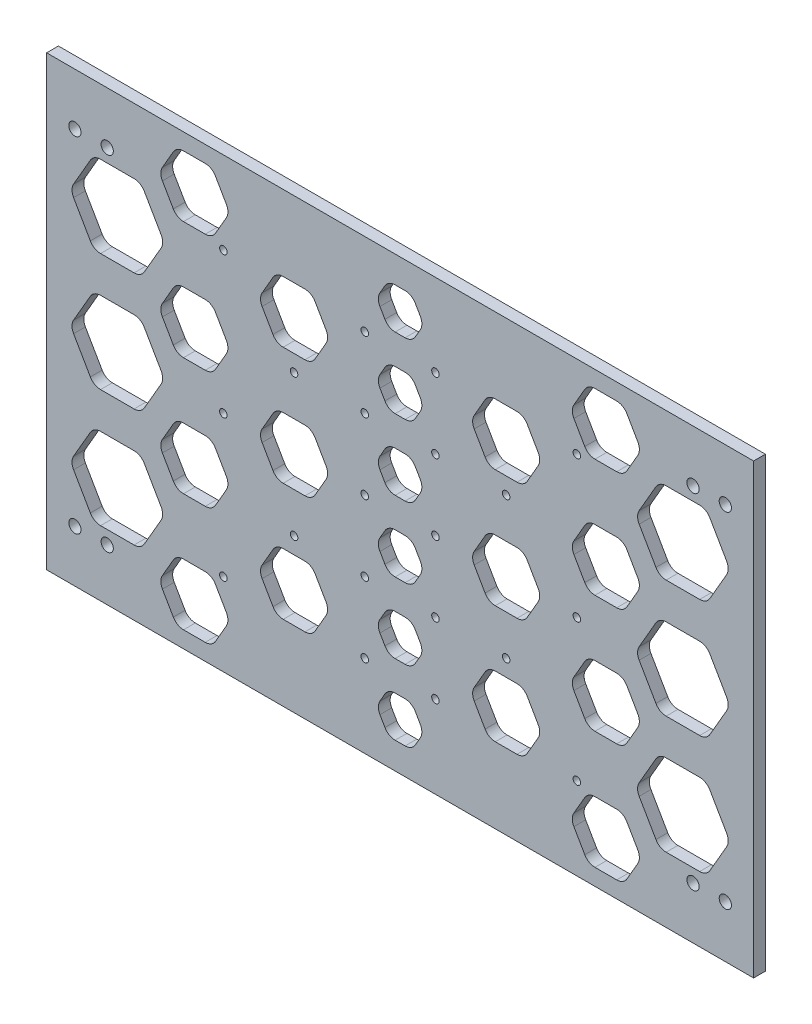
SolidWorks part; units mm, degrees
ref_plane "前视基准面" through (0, 0, 0) normal (0, 0, 1) x (1, 0, 0)
ref_plane "上视基准面" through (0, 0, 0) normal (0, 1, 0) x (1, 0, 0)
ref_plane "右视基准面" through (0, 0, 0) normal (1, 0, 0) x (0, 0, -1)
other "Configuration Table"
sketch "草图1" plane through (0, 0, 0) normal (0, 0, 1) x (1, 0, 0)
  line L0 (0, -95) -> (300, -95) construction
  line L1 (0, 0) -> (300, 0)
  line L2 (0, 0) -> (0, -190)
  line L3 (0, -190) -> (300, -190)
  line L4 (300, 0) -> (300, -190)
  line L5 (50, 0) -> (250, 0)
  line L6 (50, 0) -> (50, -50)
  line L7 (50, -50) -> (250, -50)
  line L8 (250, 0) -> (250, -50)
  line L9 (250, -190) -> (250, -140)
  line L10 (50, -140) -> (250, -140)
  line L11 (50, -190) -> (50, -140)
  dimension "D1" = 300
  dimension "D2" = 190
  dimension "D3" = 50
  dimension "D4" = 50
  dimension "D5" = 50
extrude "凸台-拉伸2" add sketch "草图1" along normal blind 5 contours L2 L0 L4 L1 L8 L7 L6 | L0 L2 L3 L11 L10 L9 L4 region at (150, -59.6622, 0) region at (150, -130.3378, 0)
sketch "草图2" plane through (0, 0, 5) normal (0, 0, 1) x (1, 0, 0)
  line L0 (0, -95) -> (300, -95) construction
  line L1 (150, -50) -> (150, -140) construction
  line L2 (0, -35) -> (5, -35)
  line L3 (0, -35) -> (0, -65)
  line L4 (0, -65) -> (5, -65)
  line L5 (5, -35) -> (5, -65)
  line L6 (0, -155) -> (5, -155)
  line L7 (5, -155) -> (5, -125)
  line L8 (0, -125) -> (5, -125)
  line L9 (300, -155) -> (295, -155)
  line L10 (295, -155) -> (295, -125)
  line L11 (300, -125) -> (295, -125)
  line L12 (0, 0) -> (0, -190)
  line L13 (0, -190) -> (50, -190)
  line L14 (50, -190) -> (50, -140)
  line L15 (50, -140) -> (250, -140)
  line L16 (250, -140) -> (250, -190)
  line L17 (250, -190) -> (300, -190)
  line L18 (300, -190) -> (300, 0)
  line L19 (300, 0) -> (250, 0)
  line L20 (250, 0) -> (250, -50)
  line L21 (250, -50) -> (50, -50)
  line L22 (50, -50) -> (50, 0)
  line L23 (50, 0) -> (0, 0)
  line L24 (0, 0) -> (0, -190)
  line L25 (0, -190) -> (50, -190)
  line L26 (50, -190) -> (50, -140)
  line L27 (50, -140) -> (250, -140)
  line L28 (250, -140) -> (250, -190)
  line L29 (250, -190) -> (300, -190)
  line L30 (300, -190) -> (300, 0)
  line L31 (300, 0) -> (250, 0)
  line L32 (250, 0) -> (250, -50)
  line L33 (250, -50) -> (50, -50)
  line L34 (50, -50) -> (50, 0)
  line L35 (50, 0) -> (0, 0)
  line L36 (300, -65) -> (295, -65)
  line L37 (300, -35) -> (295, -35)
  line L38 (295, -35) -> (295, -65)
  line M22 (0, 0) -> (0, -190)
  line M28 (300, -190) -> (300, 0)
  dimension "D2" = 30
  dimension "D3" = 30
  dimension "D4" = 5
  dimension "D1" = 0
extrude "切除-拉伸1" cut sketch "草图2" against normal blind 10 contours L5 L2 L4 M22 | L8 L6 L7 M22 | L37 L38 L36 L30 | L11 L10 L9 M28 region at (2.5, -50, 5) region at (2.5, -140, 5) region at (297.5, -50, 5) region at (297.5, -140, 5)
sketch "草图3" plane through (0, 0, 5) normal (0, 0, 1) x (1, 0, 0)
  line L0 (150, -50) -> (150, -140) construction
  line L1 (0, -95) -> (300, -95)
  line L28 (0, -65) -> (0, -125)
  line L29 (0, -125) -> (5, -125)
  line L30 (5, -125) -> (5, -155)
  line L31 (5, -155) -> (0, -155)
  line L32 (0, -155) -> (0, -190)
  line L33 (0, -190) -> (50, -190)
  line L34 (50, -190) -> (50, -140)
  line L35 (50, -140) -> (250, -140)
  line L36 (250, -140) -> (250, -190)
  line L37 (250, -190) -> (300, -190)
  line L38 (300, -190) -> (300, -155)
  line L39 (300, -155) -> (295, -155)
  line L40 (295, -155) -> (295, -125)
  line L41 (295, -125) -> (300, -125)
  line L42 (300, -125) -> (300, -65)
  line L43 (300, -65) -> (295, -65)
  line L44 (295, -65) -> (295, -35)
  line L45 (295, -35) -> (300, -35)
  line L46 (300, -35) -> (300, 0)
  line L47 (300, 0) -> (250, 0)
  line L48 (250, 0) -> (250, -50)
  line L49 (250, -50) -> (50, -50)
  line L50 (50, -50) -> (50, 0)
  line L51 (50, 0) -> (0, 0)
  line L52 (0, 0) -> (0, -35)
  line L53 (0, -35) -> (5, -35)
  line L54 (5, -35) -> (5, -65)
  line L55 (5, -65) -> (0, -65)
  line L56 (0, -65) -> (0, -125)
  line L57 (0, -125) -> (5, -125)
  line L58 (5, -125) -> (5, -155)
  line L59 (5, -155) -> (0, -155)
  line L60 (0, -155) -> (0, -190)
  line L61 (0, -190) -> (50, -190)
  line L62 (50, -190) -> (50, -140)
  line L63 (50, -140) -> (250, -140)
  line L64 (250, -140) -> (250, -190)
  line L65 (250, -190) -> (300, -190)
  line L66 (300, -190) -> (300, -155)
  line L67 (300, -155) -> (295, -155)
  line L68 (295, -155) -> (295, -125)
  line L69 (295, -125) -> (300, -125)
  line L70 (300, -125) -> (300, -65)
  line L71 (300, -65) -> (295, -65)
  line L72 (295, -65) -> (295, -35)
  line L73 (295, -35) -> (300, -35)
  line L74 (300, -35) -> (300, 0)
  line L75 (300, 0) -> (250, 0)
  line L76 (250, 0) -> (250, -50)
  line L77 (250, -50) -> (50, -50)
  line L78 (50, -50) -> (50, 0)
  line L79 (50, 0) -> (0, 0)
  line L80 (0, 0) -> (0, -35)
  line L81 (0, -35) -> (5, -35)
  line L82 (5, -35) -> (5, -65)
  line L83 (5, -65) -> (0, -65)
  circle A0 centre (5, -35) radius 1
  circle A1 centre (5, -65) radius 1
  circle A2 centre (5, -125) radius 1
  circle A3 centre (5, -155) radius 1
  circle A4 centre (295, -35) radius 1
  circle A5 centre (295, -65) radius 1
  circle A6 centre (295, -125) radius 1
  circle A7 centre (295, -155) radius 1
  line M31 (5, -125) -> (5, -155)
  line M32 (5, -155) -> (0, -155)
  line M41 (295, -155) -> (295, -125)
  line M42 (295, -125) -> (300, -125)
  line M45 (295, -65) -> (295, -35)
  line M46 (295, -35) -> (300, -35)
  line M55 (5, -35) -> (5, -65)
  line M56 (5, -65) -> (0, -65)
  dimension "D2" = 2
  dimension "D3" = 2
  dimension "D1" = 0
extrude "切除-拉伸2" cut sketch "草图3" against normal blind 10 contours A0 L81 M55 | L81 A0 M55 | A1 M56 M55 | A2 L57 M31 | A3 M31 M32 | A7 L67 M41 | A6 L68 M42 | A4 L72 M46 | A5 L71 M45 region at (5.1415, -65.1415, 5) region at (5.1415, -124.8585, 5) region at (294.8585, -124.8585, 5) region at (294.8585, -65.1415, 5) region at (4.5756, -35.4244, 5) region at (5.1415, -34.8585, 5) region at (5.1415, -155.1415, 5) region at (294.8585, -155.1415, 5) region at (294.8585, -34.8585, 5)
sketch "草图4" plane through (50, 0, 0) normal (1, 0, 0) x (0, 0, -1)
  line L4 (0, -50) -> (0, 0)
  line L5 (0, 0) -> (-5, 0)
  line L6 (-5, 0) -> (-5, -50)
  line L7 (-5, -50) -> (0, -50)
  line L8 (0, -50) -> (0, 0)
  line L9 (0, 0) -> (-5, 0)
  line L10 (-5, 0) -> (-5, -50)
  line L11 (-5, -50) -> (0, -50)
  line L12 (0, -190) -> (0, -140)
  line L13 (0, -140) -> (-5, -140)
  line L14 (-5, -140) -> (-5, -190)
  line L15 (-5, -190) -> (0, -190)
  line L16 (0, -190) -> (0, -140)
  line L17 (0, -140) -> (-5, -140)
  line L18 (-5, -140) -> (-5, -190)
  line L19 (-5, -190) -> (0, -190)
  dimension "D1" = 0
  dimension "D2" = 0
extrude "凸台-拉伸3" add sketch "草图4" along normal up to next
sketch "草图5" plane through (0, 0, 5) normal (0, 0, 1) x (1, 0, 0)
  line L0 (150, 0) -> (150, -190)
  line L1 (32.7, -35) -> (37.7, -35)
  line L2 (32.7, -35) -> (32.7, -65)
  line L3 (32.7, -65) -> (37.7, -65)
  line L4 (37.7, -35) -> (37.7, -65)
  line L5 (0, -95) -> (300, -95)
  line L6 (32.7, -125) -> (37.7, -125)
  line L7 (37.7, -155) -> (37.7, -125)
  line L8 (32.7, -155) -> (37.7, -155)
  line L9 (32.7, -155) -> (32.7, -125)
  line L10 (267.3, -155) -> (267.3, -125)
  line L11 (267.3, -155) -> (262.3, -155)
  line L12 (262.3, -155) -> (262.3, -125)
  line L13 (267.3, -125) -> (262.3, -125)
  line L14 (267.3, -65) -> (262.3, -65)
  line L15 (262.3, -35) -> (262.3, -65)
  line L16 (267.3, -35) -> (262.3, -35)
  line L17 (267.3, -35) -> (267.3, -65)
  line L20 (300, 0) -> (0, 0)
  line L21 (0, 0) -> (0, -35)
  line L22 (0, -35) -> (4, -35)
  line L23 (5, -36) -> (5, -64)
  line L24 (4, -65) -> (0, -65)
  line L25 (0, -65) -> (0, -125)
  line L26 (0, -125) -> (4, -125)
  line L27 (5, -126) -> (5, -154)
  line L28 (4, -155) -> (0, -155)
  line L29 (0, -155) -> (0, -190)
  line L30 (0, -190) -> (300, -190)
  line L31 (300, -190) -> (300, -155)
  line L32 (300, -155) -> (296, -155)
  line L33 (295, -154) -> (295, -126)
  line L34 (296, -125) -> (300, -125)
  line L35 (300, -125) -> (300, -65)
  line L36 (300, -65) -> (296, -65)
  line L37 (295, -64) -> (295, -36)
  line L38 (296, -35) -> (300, -35)
  line L39 (300, -35) -> (300, 0)
  line L40 (300, 0) -> (0, 0)
  line L41 (0, 0) -> (0, -35)
  line L42 (0, -35) -> (4, -35)
  line L43 (5, -36) -> (5, -64)
  line L44 (4, -65) -> (0, -65)
  line L45 (0, -65) -> (0, -125)
  line L46 (0, -125) -> (4, -125)
  line L47 (5, -126) -> (5, -154)
  line L48 (4, -155) -> (0, -155)
  line L49 (0, -155) -> (0, -190)
  line L50 (0, -190) -> (300, -190)
  line L51 (300, -190) -> (300, -155)
  line L52 (300, -155) -> (296, -155)
  line L53 (295, -154) -> (295, -126)
  line L54 (296, -125) -> (300, -125)
  line L55 (300, -125) -> (300, -65)
  line L56 (300, -65) -> (296, -65)
  line L57 (295, -64) -> (295, -36)
  line L58 (296, -35) -> (300, -35)
  line L59 (300, -35) -> (300, 0)
  circle A0 centre (32.7, -35) radius 1
  circle A1 centre (37.7, -35) radius 1
  circle A2 centre (32.7, -65) radius 1
  circle A3 centre (37.7, -65) radius 1
  circle A4 centre (37.7, -125) radius 1
  circle A5 centre (32.7, -125) radius 1
  circle A6 centre (37.7, -155) radius 1
  circle A7 centre (32.7, -155) radius 1
  arc A8 (5, -36) -> (4, -35) centre (5, -35) ccw
  arc A9 (4, -65) -> (5, -64) centre (5, -65) ccw
  arc A10 (5, -126) -> (4, -125) centre (5, -125) ccw
  arc A11 (4, -155) -> (5, -154) centre (5, -155) ccw
  arc A12 (295, -154) -> (296, -155) centre (295, -155) ccw
  arc A13 (296, -125) -> (295, -126) centre (295, -125) ccw
  arc A14 (295, -64) -> (296, -65) centre (295, -65) ccw
  arc A15 (296, -35) -> (295, -36) centre (295, -35) ccw
  arc A16 (5, -36) -> (4, -35) centre (5, -35) ccw
  arc A17 (4, -65) -> (5, -64) centre (5, -65) ccw
  arc A18 (5, -126) -> (4, -125) centre (5, -125) ccw
  arc A19 (4, -155) -> (5, -154) centre (5, -155) ccw
  arc A20 (295, -154) -> (296, -155) centre (295, -155) ccw
  arc A21 (296, -125) -> (295, -126) centre (295, -125) ccw
  arc A22 (295, -64) -> (296, -65) centre (295, -65) ccw
  arc A23 (296, -35) -> (295, -36) centre (295, -35) ccw
  circle A24 centre (262.3, -155) radius 1
  circle A25 centre (267.3, -155) radius 1
  circle A26 centre (262.3, -125) radius 1
  circle A27 centre (267.3, -125) radius 1
  circle A28 centre (262.3, -35) radius 1
  circle A29 centre (267.3, -35) radius 1
  circle A30 centre (267.3, -65) radius 1
  circle A31 centre (262.3, -65) radius 1
  dimension "D4" = 2
  dimension "D5" = 2
  dimension "D6" = 2
  dimension "D7" = 2
  dimension "D2" = 32.7
  dimension "D3" = 5
  dimension "D1" = 0
extrude "切除-拉伸3" cut sketch "草图5" against normal blind 5 contours A3 L4 A1 L1 A0 L2 A2 L3 | L1 A0 L2 | L4 A1 L1 | L1 A1 L4 | L2 A0 L1 | L3 A2 L2 | L2 A2 L3 | L3 A3 L4 | L4 A3 L3 | A7 L8 L9 | A7 L9 L8 | L9 A7 L8 A6 L7 A4 L6 A5 | A6 L8 L7 | A6 L7 L8 | A5 L9 L6 | A5 L6 L9 | A4 L6 L7 | A4 L7 L6 | L15 A31 L14 A30 L17 A29 L16 A28 | A28 L15 L16 | A28 L16 L15 | A29 L17 L16 | A29 L16 L17 | A31 L15 L14 | A31 L14 L15 | A30 L17 L14 | A30 L14 L17 | L13 A26 L12 | L12 A26 L13 | A27 L13 A26 L12 A24 L11 A25 L10 | L13 A27 L10 | L10 A27 L13 | L12 A24 L11 | L11 A24 L12 | L11 A25 L10 | L10 A25 L11 region at (32.5585, -34.8585, 5) region at (33.1244, -35.4244, 5) region at (35.2, -50, 5) region at (37.8415, -34.8585, 5) region at (37.2756, -35.4244, 5) region at (33.1244, -64.5756, 5) region at (32.5585, -65.1415, 5) region at (37.8415, -65.1415, 5) region at (37.2756, -64.5756, 5) region at (32.5585, -124.8585, 5) region at (33.1244, -125.4244, 5) region at (35.2, -140, 5) region at (37.8415, -124.8585, 5) region at (37.2756, -125.4244, 5) region at (33.1244, -154.5756, 5) region at (32.5585, -155.1415, 5) region at (37.8415, -155.1415, 5) region at (37.2756, -154.5756, 5) region at (266.8756, -154.5756, 5) region at (267.4415, -155.1415, 5) region at (264.8, -140, 5) region at (266.8756, -125.4244, 5) region at (267.4415, -124.8585, 5) region at (262.1585, -155.1415, 5) region at (262.7244, -154.5756, 5) region at (262.7244, -125.4244, 5) region at (262.1585, -124.8585, 5) region at (262.1585, -65.1415, 5) region at (264.8, -50, 5) region at (262.7244, -64.5756, 5) region at (266.8756, -64.5756, 5) region at (267.4415, -65.1415, 5) region at (262.1585, -34.8585, 5) region at (262.7244, -35.4244, 5) region at (266.8756, -35.4244, 5) region at (267.4415, -34.8585, 5)
sketch "草图6" plane through (0, 0, 5) normal (0, 0, 1) x (1, 0, 0)
  line L0 (4, -160) -> (127.3647, -160)
  line L1 (32.7, -154) -> (32.7, -126) construction
  line L2 (0, -95) -> (300, -95)
  line L3 (150, 0) -> (150, -190)
  line L20 (300, 0) -> (0, 0)
  line L21 (0, 0) -> (0, -35)
  line L22 (0, -35) -> (4, -35)
  line L23 (5, -36) -> (5, -64)
  line L24 (4, -65) -> (0, -65)
  line L25 (0, -65) -> (0, -125)
  line L26 (0, -125) -> (4, -125)
  line L27 (5, -126) -> (5, -154)
  line L28 (4, -155) -> (0, -155)
  line L29 (0, -155) -> (0, -190)
  line L30 (0, -190) -> (300, -190)
  line L31 (300, -190) -> (300, -155)
  line L32 (300, -155) -> (296, -155)
  line L33 (295, -154) -> (295, -126)
  line L34 (296, -125) -> (300, -125)
  line L35 (300, -125) -> (300, -65)
  line L36 (300, -65) -> (296, -65)
  line L37 (295, -64) -> (295, -36)
  line L38 (296, -35) -> (300, -35)
  line L39 (300, -35) -> (300, 0)
  line L40 (300, 0) -> (0, 0)
  line L41 (0, 0) -> (0, -35)
  line L42 (0, -35) -> (4, -35)
  line L43 (5, -36) -> (5, -64)
  line L44 (4, -65) -> (0, -65)
  line L45 (0, -65) -> (0, -125)
  line L46 (0, -125) -> (4, -125)
  line L47 (5, -126) -> (5, -154)
  line L48 (4, -155) -> (0, -155)
  line L49 (0, -155) -> (0, -190)
  line L50 (0, -190) -> (300, -190)
  line L51 (300, -190) -> (300, -155)
  line L52 (300, -155) -> (296, -155)
  line L53 (295, -154) -> (295, -126)
  line L54 (296, -125) -> (300, -125)
  line L55 (300, -125) -> (300, -65)
  line L56 (300, -65) -> (296, -65)
  line L57 (295, -64) -> (295, -36)
  line L58 (296, -35) -> (300, -35)
  line L59 (300, -35) -> (300, 0)
  circle A0 centre (12, -168) radius 2.6
  circle A1 centre (25.7, -168) radius 2.6
  circle A2 centre (25.7, -22) radius 2.6
  circle A3 centre (12, -22) radius 2.6
  circle A4 centre (274.3, -168) radius 2.6
  circle A5 centre (288, -168) radius 2.6
  circle A6 centre (274.3, -22) radius 2.6
  circle A7 centre (288, -22) radius 2.6
  arc A8 (5, -36) -> (4, -35) centre (5, -35) ccw
  arc A9 (4, -65) -> (5, -64) centre (5, -65) ccw
  arc A10 (5, -126) -> (4, -125) centre (5, -125) ccw
  arc A11 (4, -155) -> (5, -154) centre (5, -155) ccw
  arc A12 (295, -154) -> (296, -155) centre (295, -155) ccw
  arc A13 (296, -125) -> (295, -126) centre (295, -125) ccw
  arc A14 (295, -64) -> (296, -65) centre (295, -65) ccw
  arc A15 (296, -35) -> (295, -36) centre (295, -35) ccw
  arc A16 (5, -36) -> (4, -35) centre (5, -35) ccw
  arc A17 (4, -65) -> (5, -64) centre (5, -65) ccw
  arc A18 (5, -126) -> (4, -125) centre (5, -125) ccw
  arc A19 (4, -155) -> (5, -154) centre (5, -155) ccw
  arc A20 (295, -154) -> (296, -155) centre (295, -155) ccw
  arc A21 (296, -125) -> (295, -126) centre (295, -125) ccw
  arc A22 (295, -64) -> (296, -65) centre (295, -65) ccw
  arc A23 (296, -35) -> (295, -36) centre (295, -35) ccw
  dimension "D3" = 5.2
  dimension "D4" = 5.2
  dimension "D5" = 8
  dimension "D2" = 30
  dimension "D6" = 7
  dimension "D7" = 8
  dimension "D8" = 7
  dimension "D1" = 0
extrude "切除-拉伸4" cut sketch "草图6" against normal through all contours A3 | A2 | A0 | A1 | A4 | A5 | A6 | A7 region at (12, -168, 5) region at (25.7, -168, 5) region at (25.7, -22, 5) region at (12, -22, 5) region at (274.3, -168, 5) region at (288, -168, 5) region at (274.3, -22, 5) region at (288, -22, 5)
sketch "草图7" plane through (0, 0, 5) normal (0, 0, 1) x (1, 0, 0)
  line L1 (0, 0) -> (300, 0) construction
  line L6 (300, 0) -> (300, -35) construction
  circle A0 centre (75, -35) radius 1.6
  circle A1 centre (105, -35) radius 1.6
  circle A2 centre (135, -35) radius 1.6
  circle A3 centre (165, -35) radius 1.6
  circle A4 centre (195, -35) radius 1.6
  circle A5 centre (225, -35) radius 1.6
  circle A6 centre (105, -65) radius 1.6
  circle A7 centre (135, -65) radius 1.6
  circle A8 centre (165, -65) radius 1.6
  circle A9 centre (195, -65) radius 1.6
  circle A10 centre (225, -65) radius 1.6
  circle A11 centre (105, -95) radius 1.6
  circle A12 centre (135, -95) radius 1.6
  circle A13 centre (165, -95) radius 1.6
  circle A14 centre (195, -95) radius 1.6
  circle A15 centre (225, -95) radius 1.6
  circle A16 centre (105, -125) radius 1.6
  circle A17 centre (135, -125) radius 1.6
  circle A18 centre (165, -125) radius 1.6
  circle A19 centre (195, -125) radius 1.6
  circle A20 centre (225, -125) radius 1.6
  circle A21 centre (105, -155) radius 1.6
  circle A22 centre (135, -155) radius 1.6
  circle A23 centre (165, -155) radius 1.6
  circle A24 centre (195, -155) radius 1.6
  circle A25 centre (225, -155) radius 1.6
  circle A26 centre (75, -65) radius 1.6
  circle A27 centre (75, -95) radius 1.6
  circle A28 centre (75, -125) radius 1.6
  circle A29 centre (75, -155) radius 1.6
  dimension "D1" = 3.2
  dimension "D2" = 35
  dimension "D5" = 75
  dimension "D6" = 30
  dimension "D7" = 30
  dimension "D3" = 6
  dimension "D4" = 5
extrude "切除-拉伸5" cut sketch "草图7" against normal through all
sketch "草图8" plane through (0, 0, 5) normal (0, 0, 1) x (1, 0, 0)
  line L4 (267.3, -154) -> (267.3, -126)
  line L5 (263.3, -155) -> (266.3, -155)
  line L6 (262.3, -126) -> (262.3, -154)
  line L7 (266.3, -125) -> (263.3, -125)
  line L8 (267.3, -154) -> (267.3, -126)
  line L9 (263.3, -155) -> (266.3, -155)
  line L10 (262.3, -126) -> (262.3, -154)
  line L11 (266.3, -125) -> (263.3, -125)
  line L12 (32.7, -36) -> (32.7, -64)
  line L13 (36.7, -35) -> (33.7, -35)
  line L14 (37.7, -64) -> (37.7, -36)
  line L15 (33.7, -65) -> (36.7, -65)
  line L16 (32.7, -36) -> (32.7, -64)
  line L17 (36.7, -35) -> (33.7, -35)
  line L18 (37.7, -64) -> (37.7, -36)
  line L19 (33.7, -65) -> (36.7, -65)
  line L20 (263.3, -65) -> (266.3, -65)
  line L21 (262.3, -36) -> (262.3, -64)
  line L22 (266.3, -35) -> (263.3, -35)
  line L23 (267.3, -64) -> (267.3, -36)
  line L24 (263.3, -65) -> (266.3, -65)
  line L25 (262.3, -36) -> (262.3, -64)
  line L26 (266.3, -35) -> (263.3, -35)
  line L27 (267.3, -64) -> (267.3, -36)
  line L28 (36.7, -125) -> (33.7, -125)
  line L29 (37.7, -154) -> (37.7, -126)
  line L30 (33.7, -155) -> (36.7, -155)
  line L31 (32.7, -126) -> (32.7, -154)
  line L32 (36.7, -125) -> (33.7, -125)
  line L33 (37.7, -154) -> (37.7, -126)
  line L34 (33.7, -155) -> (36.7, -155)
  line L35 (32.7, -126) -> (32.7, -154)
  line L52 (300, 0) -> (0, 0)
  line L53 (0, 0) -> (0, -35)
  line L54 (0, -35) -> (4, -35)
  line L55 (5, -36) -> (5, -64)
  line L56 (4, -65) -> (0, -65)
  line L57 (0, -65) -> (0, -125)
  line L58 (0, -125) -> (4, -125)
  line L59 (5, -126) -> (5, -154)
  line L60 (4, -155) -> (0, -155)
  line L61 (0, -155) -> (0, -190)
  line L62 (0, -190) -> (300, -190)
  line L63 (300, -190) -> (300, -155)
  line L64 (300, -155) -> (296, -155)
  line L65 (295, -154) -> (295, -126)
  line L66 (296, -125) -> (300, -125)
  line L67 (300, -125) -> (300, -65)
  line L68 (300, -65) -> (296, -65)
  line L69 (295, -64) -> (295, -36)
  line L70 (296, -35) -> (300, -35)
  line L71 (300, -35) -> (300, 0)
  line L72 (300, 0) -> (0, 0)
  line L73 (0, 0) -> (0, -35)
  line L74 (0, -35) -> (4, -35)
  line L75 (5, -36) -> (5, -64)
  line L76 (4, -65) -> (0, -65)
  line L77 (0, -65) -> (0, -125)
  line L78 (0, -125) -> (4, -125)
  line L79 (5, -126) -> (5, -154)
  line L80 (4, -155) -> (0, -155)
  line L81 (0, -155) -> (0, -190)
  line L82 (0, -190) -> (300, -190)
  line L83 (300, -190) -> (300, -155)
  line L84 (300, -155) -> (296, -155)
  line L85 (295, -154) -> (295, -126)
  line L86 (296, -125) -> (300, -125)
  line L87 (300, -125) -> (300, -65)
  line L88 (300, -65) -> (296, -65)
  line L89 (295, -64) -> (295, -36)
  line L90 (296, -35) -> (300, -35)
  line L91 (300, -35) -> (300, 0)
  circle A1 centre (195, -65) radius 1.6
  circle A2 centre (195, -65) radius 1.6
  circle A3 centre (12, -22) radius 2.6
  circle A4 centre (12, -22) radius 2.6
  circle A5 centre (274.3, -22) radius 2.6
  circle A6 centre (274.3, -22) radius 2.6
  circle A7 centre (288, -22) radius 2.6
  arc A8 (267.3, -126) -> (266.3, -125) centre (267.3, -125) ccw
  arc A9 (266.3, -155) -> (267.3, -154) centre (267.3, -155) ccw
  arc A10 (262.3, -154) -> (263.3, -155) centre (262.3, -155) ccw
  arc A11 (263.3, -125) -> (262.3, -126) centre (262.3, -125) ccw
  arc A12 (267.3, -126) -> (266.3, -125) centre (267.3, -125) ccw
  arc A13 (266.3, -155) -> (267.3, -154) centre (267.3, -155) ccw
  arc A14 (262.3, -154) -> (263.3, -155) centre (262.3, -155) ccw
  arc A15 (263.3, -125) -> (262.3, -126) centre (262.3, -125) ccw
  arc A16 (32.7, -64) -> (33.7, -65) centre (32.7, -65) ccw
  arc A17 (33.7, -35) -> (32.7, -36) centre (32.7, -35) ccw
  arc A18 (37.7, -36) -> (36.7, -35) centre (37.7, -35) ccw
  arc A19 (36.7, -65) -> (37.7, -64) centre (37.7, -65) ccw
  arc A20 (32.7, -64) -> (33.7, -65) centre (32.7, -65) ccw
  arc A21 (33.7, -35) -> (32.7, -36) centre (32.7, -35) ccw
  arc A22 (37.7, -36) -> (36.7, -35) centre (37.7, -35) ccw
  arc A23 (36.7, -65) -> (37.7, -64) centre (37.7, -65) ccw
  arc A24 (266.3, -65) -> (267.3, -64) centre (267.3, -65) ccw
  arc A25 (262.3, -64) -> (263.3, -65) centre (262.3, -65) ccw
  arc A26 (263.3, -35) -> (262.3, -36) centre (262.3, -35) ccw
  arc A27 (267.3, -36) -> (266.3, -35) centre (267.3, -35) ccw
  arc A28 (266.3, -65) -> (267.3, -64) centre (267.3, -65) ccw
  arc A29 (262.3, -64) -> (263.3, -65) centre (262.3, -65) ccw
  arc A30 (263.3, -35) -> (262.3, -36) centre (262.3, -35) ccw
  arc A31 (267.3, -36) -> (266.3, -35) centre (267.3, -35) ccw
  arc A32 (33.7, -125) -> (32.7, -126) centre (32.7, -125) ccw
  arc A33 (37.7, -126) -> (36.7, -125) centre (37.7, -125) ccw
  arc A34 (36.7, -155) -> (37.7, -154) centre (37.7, -155) ccw
  arc A35 (32.7, -154) -> (33.7, -155) centre (32.7, -155) ccw
  arc A36 (33.7, -125) -> (32.7, -126) centre (32.7, -125) ccw
  arc A37 (37.7, -126) -> (36.7, -125) centre (37.7, -125) ccw
  arc A38 (36.7, -155) -> (37.7, -154) centre (37.7, -155) ccw
  arc A39 (32.7, -154) -> (33.7, -155) centre (32.7, -155) ccw
  circle A40 centre (288, -22) radius 2.6
  circle A41 centre (12, -168) radius 2.6
  circle A42 centre (12, -168) radius 2.6
  circle A43 centre (25.7, -168) radius 2.6
  circle A44 centre (25.7, -168) radius 2.6
  circle A45 centre (288, -168) radius 2.6
  circle A46 centre (288, -168) radius 2.6
  circle A47 centre (25.7, -22) radius 2.6
  circle A48 centre (25.7, -22) radius 2.6
  circle A49 centre (274.3, -168) radius 2.6
  circle A50 centre (274.3, -168) radius 2.6
  circle A51 centre (75, -35) radius 1.6
  circle A52 centre (75, -35) radius 1.6
  circle A53 centre (195, -35) radius 1.6
  circle A54 centre (195, -35) radius 1.6
  circle A55 centre (165, -65) radius 1.6
  circle A56 centre (165, -65) radius 1.6
  circle A57 centre (135, -65) radius 1.6
  circle A58 centre (135, -65) radius 1.6
  circle A59 centre (105, -65) radius 1.6
  circle A60 centre (105, -65) radius 1.6
  circle A61 centre (225, -35) radius 1.6
  circle A62 centre (225, -35) radius 1.6
  circle A63 centre (75, -125) radius 1.6
  circle A64 centre (75, -125) radius 1.6
  circle A65 centre (75, -95) radius 1.6
  circle A66 centre (75, -95) radius 1.6
  circle A67 centre (75, -65) radius 1.6
  circle A68 centre (75, -65) radius 1.6
  circle A69 centre (225, -155) radius 1.6
  circle A70 centre (225, -155) radius 1.6
  circle A71 centre (75, -155) radius 1.6
  circle A72 centre (75, -155) radius 1.6
  circle A73 centre (195, -155) radius 1.6
  circle A74 centre (195, -155) radius 1.6
  circle A75 centre (165, -155) radius 1.6
  circle A76 centre (165, -155) radius 1.6
  circle A77 centre (135, -155) radius 1.6
  circle A78 centre (135, -155) radius 1.6
  circle A79 centre (105, -155) radius 1.6
  circle A80 centre (105, -155) radius 1.6
  circle A81 centre (225, -125) radius 1.6
  circle A82 centre (225, -125) radius 1.6
  circle A83 centre (195, -125) radius 1.6
  circle A84 centre (195, -125) radius 1.6
  circle A85 centre (165, -125) radius 1.6
  circle A86 centre (165, -125) radius 1.6
  circle A87 centre (135, -125) radius 1.6
  circle A88 centre (135, -125) radius 1.6
  circle A89 centre (165, -35) radius 1.6
  circle A90 centre (165, -35) radius 1.6
  circle A91 centre (135, -35) radius 1.6
  circle A92 centre (135, -35) radius 1.6
  circle A93 centre (105, -35) radius 1.6
  circle A94 centre (105, -35) radius 1.6
  circle A95 centre (165, -95) radius 1.6
  circle A96 centre (165, -95) radius 1.6
  circle A97 centre (195, -95) radius 1.6
  circle A98 centre (195, -95) radius 1.6
  circle A99 centre (105, -125) radius 1.6
  circle A100 centre (105, -125) radius 1.6
  circle A101 centre (225, -95) radius 1.6
  circle A102 centre (225, -95) radius 1.6
  circle A103 centre (135, -95) radius 1.6
  circle A104 centre (135, -95) radius 1.6
  circle A105 centre (105, -95) radius 1.6
  circle A106 centre (105, -95) radius 1.6
  circle A107 centre (225, -65) radius 1.6
  circle A108 centre (225, -65) radius 1.6
  arc A116 (5, -36) -> (4, -35) centre (5, -35) ccw
  arc A117 (4, -65) -> (5, -64) centre (5, -65) ccw
  arc A118 (5, -126) -> (4, -125) centre (5, -125) ccw
  arc A119 (4, -155) -> (5, -154) centre (5, -155) ccw
  arc A120 (295, -154) -> (296, -155) centre (295, -155) ccw
  arc A121 (296, -125) -> (295, -126) centre (295, -125) ccw
  arc A122 (295, -64) -> (296, -65) centre (295, -65) ccw
  arc A123 (296, -35) -> (295, -36) centre (295, -35) ccw
  arc A124 (5, -36) -> (4, -35) centre (5, -35) ccw
  arc A125 (4, -65) -> (5, -64) centre (5, -65) ccw
  arc A126 (5, -126) -> (4, -125) centre (5, -125) ccw
  arc A127 (4, -155) -> (5, -154) centre (5, -155) ccw
  arc A128 (295, -154) -> (296, -155) centre (295, -155) ccw
  arc A129 (296, -125) -> (295, -126) centre (295, -125) ccw
  arc A130 (295, -64) -> (296, -65) centre (295, -65) ccw
  arc A131 (296, -35) -> (295, -36) centre (295, -35) ccw
  dimension "D1" = 0
  dimension "D2" = 0
  dimension "D3" = 0
  dimension "D4" = 0
  dimension "D5" = 0
  dimension "D6" = 0
  dimension "D7" = 0
  dimension "D8" = 0
  dimension "D9" = 0
  dimension "D10" = 0
  dimension "D11" = 0
  dimension "D12" = 0
  dimension "D13" = 0
  dimension "D14" = 0
  dimension "D15" = 0
  dimension "D16" = 0
  dimension "D17" = 0
  dimension "D18" = 0
  dimension "D19" = 0
  dimension "D20" = 0
  dimension "D21" = 0
  dimension "D22" = 0
  dimension "D23" = 0
  dimension "D24" = 0
  dimension "D25" = 0
  dimension "D26" = 0
  dimension "D27" = 0
  dimension "D28" = 0
  dimension "D29" = 0
  dimension "D30" = 0
  dimension "D31" = 0
  dimension "D32" = 0
  dimension "D33" = 0
  dimension "D34" = 0
  dimension "D35" = 0
  dimension "D36" = 0
  dimension "D37" = 0
  dimension "D38" = 0
  dimension "D39" = 0
  dimension "D40" = 0
  dimension "D41" = 0
  dimension "D42" = 0
  dimension "D43" = 0
sketch "草图9" plane through (0, 0, 5) normal (0, 0, 1) x (1, 0, 0)
  line L0 (300, 0) -> (0, 0) construction
  line L1 (77.7, -20.0004) -> (70.2, -7.01)
  line L2 (70.2, -7.01) -> (55.2, -7.01)
  line L3 (55.2, -7.01) -> (47.7, -20.0004)
  line L4 (47.7, -20.0004) -> (55.2, -32.9908)
  line L5 (55.2, -32.9908) -> (70.2, -32.9908)
  line L6 (70.2, -32.9908) -> (77.7, -20.0004)
  line L7 (37.7, -64) -> (37.7, -36) construction
  line L8 (77.7, -70.0004) -> (70.2, -57.01)
  line L9 (70.2, -57.01) -> (55.2, -57.01)
  line L10 (55.2, -57.01) -> (47.7, -70.0004)
  line L11 (47.7, -70.0004) -> (55.2, -82.9908)
  line L12 (55.2, -82.9908) -> (70.2, -82.9908)
  line L13 (70.2, -82.9908) -> (77.7, -70.0004)
  line L14 (77.7, -120.0004) -> (70.2, -107.01)
  line L15 (70.2, -107.01) -> (55.2, -107.01)
  line L16 (55.2, -107.01) -> (47.7, -120.0004)
  line L17 (47.7, -120.0004) -> (55.2, -132.9908)
  line L18 (55.2, -132.9908) -> (70.2, -132.9908)
  line L19 (70.2, -132.9908) -> (77.7, -120.0004)
  line L20 (77.7, -170.0004) -> (70.2, -157.01)
  line L21 (70.2, -157.01) -> (55.2, -157.01)
  line L22 (55.2, -157.01) -> (47.7, -170.0004)
  line L23 (47.7, -170.0004) -> (55.2, -182.9908)
  line L24 (55.2, -182.9908) -> (70.2, -182.9908)
  line L25 (70.2, -182.9908) -> (77.7, -170.0004)
  line L26 (150, 0) -> (150, -190)
  line L27 (0, -95) -> (300, -95)
  line L28 (120, -45) -> (112.5, -32.0096)
  line L29 (112.5, -32.0096) -> (97.5, -32.0096)
  line L30 (97.5, -32.0096) -> (90, -45)
  line L31 (90, -45) -> (97.5, -57.9904)
  line L32 (97.5, -57.9904) -> (112.5, -57.9904)
  line L33 (112.5, -57.9904) -> (120, -45)
  line L34 (112.5, -82.0096) -> (97.5, -82.0096)
  line L35 (97.5, -82.0096) -> (90, -95)
  line L36 (90, -95) -> (97.5, -107.9904)
  line L37 (97.5, -107.9904) -> (112.5, -107.9904)
  line L38 (112.5, -107.9904) -> (120, -95)
  line L39 (120, -95) -> (112.5, -82.0096)
  line L46 (300, 0) -> (0, 0)
  line L47 (0, 0) -> (0, -35)
  line L48 (0, -35) -> (4, -35)
  line L49 (5, -36) -> (5, -64)
  line L50 (4, -65) -> (0, -65)
  line L51 (0, -65) -> (0, -125)
  line L52 (0, -125) -> (4, -125)
  line L53 (5, -126) -> (5, -154)
  line L54 (4, -155) -> (0, -155)
  line L55 (0, -155) -> (0, -190)
  line L56 (0, -190) -> (300, -190)
  line L57 (300, -190) -> (300, -155)
  line L58 (300, -155) -> (296, -155)
  line L59 (295, -154) -> (295, -126)
  line L60 (296, -125) -> (300, -125)
  line L61 (300, -125) -> (300, -65)
  line L62 (300, -65) -> (296, -65)
  line L63 (295, -64) -> (295, -36)
  line L64 (296, -35) -> (300, -35)
  line L65 (300, -35) -> (300, 0)
  line L66 (300, 0) -> (0, 0)
  line L67 (0, 0) -> (0, -35)
  line L68 (0, -35) -> (4, -35)
  line L69 (5, -36) -> (5, -64)
  line L70 (4, -65) -> (0, -65)
  line L71 (0, -65) -> (0, -125)
  line L72 (0, -125) -> (4, -125)
  line L73 (5, -126) -> (5, -154)
  line L74 (4, -155) -> (0, -155)
  line L75 (0, -155) -> (0, -190)
  line L76 (0, -190) -> (300, -190)
  line L77 (300, -190) -> (300, -155)
  line L78 (300, -155) -> (296, -155)
  line L79 (295, -154) -> (295, -126)
  line L80 (296, -125) -> (300, -125)
  line L81 (300, -125) -> (300, -65)
  line L82 (300, -65) -> (296, -65)
  line L83 (295, -64) -> (295, -36)
  line L84 (296, -35) -> (300, -35)
  line L85 (300, -35) -> (300, 0)
  line L86 (112.5, -157.9904) -> (97.5, -157.9904)
  line L87 (97.5, -157.9904) -> (90, -145)
  line L88 (90, -145) -> (97.5, -132.0096)
  line L89 (97.5, -132.0096) -> (112.5, -132.0096)
  line L90 (112.5, -132.0096) -> (120, -145)
  line L91 (120, -145) -> (112.5, -157.9904)
  line L92 (229.8, -182.9908) -> (222.3, -170.0004)
  line L93 (244.8, -182.9908) -> (229.8, -182.9908)
  line L94 (252.3, -170.0004) -> (244.8, -182.9908)
  line L95 (244.8, -157.01) -> (252.3, -170.0004)
  line L96 (229.8, -157.01) -> (244.8, -157.01)
  line L97 (222.3, -170.0004) -> (229.8, -157.01)
  line L98 (180, -145) -> (187.5, -157.9904)
  line L99 (187.5, -132.0096) -> (180, -145)
  line L100 (202.5, -132.0096) -> (187.5, -132.0096)
  line L101 (210, -145) -> (202.5, -132.0096)
  line L102 (202.5, -157.9904) -> (210, -145)
  line L103 (187.5, -157.9904) -> (202.5, -157.9904)
  line L104 (229.8, -132.9908) -> (222.3, -120.0004)
  line L105 (244.8, -132.9908) -> (229.8, -132.9908)
  line L106 (252.3, -120.0004) -> (244.8, -132.9908)
  line L107 (244.8, -107.01) -> (252.3, -120.0004)
  line L108 (229.8, -107.01) -> (244.8, -107.01)
  line L109 (222.3, -120.0004) -> (229.8, -107.01)
  line L110 (180, -95) -> (187.5, -82.0096)
  line L111 (187.5, -107.9904) -> (180, -95)
  line L112 (202.5, -107.9904) -> (187.5, -107.9904)
  line L113 (210, -95) -> (202.5, -107.9904)
  line L114 (202.5, -82.0096) -> (210, -95)
  line L115 (187.5, -82.0096) -> (202.5, -82.0096)
  line L116 (229.8, -82.9908) -> (222.3, -70.0004)
  line L117 (244.8, -82.9908) -> (229.8, -82.9908)
  line L118 (252.3, -70.0004) -> (244.8, -82.9908)
  line L119 (244.8, -57.01) -> (252.3, -70.0004)
  line L120 (229.8, -57.01) -> (244.8, -57.01)
  line L121 (222.3, -70.0004) -> (229.8, -57.01)
  line L122 (187.5, -57.9904) -> (180, -45)
  line L123 (202.5, -57.9904) -> (187.5, -57.9904)
  line L124 (210, -45) -> (202.5, -57.9904)
  line L125 (202.5, -32.0096) -> (210, -45)
  line L126 (187.5, -32.0096) -> (202.5, -32.0096)
  line L127 (180, -45) -> (187.5, -32.0096)
  line L128 (229.8, -32.9908) -> (222.3, -20.0004)
  line L129 (244.8, -32.9908) -> (229.8, -32.9908)
  line L130 (252.3, -20.0004) -> (244.8, -32.9908)
  line L131 (244.8, -7.01) -> (252.3, -20.0004)
  line L132 (229.8, -7.01) -> (244.8, -7.01)
  line L133 (222.3, -20.0004) -> (229.8, -7.01)
  circle A0 centre (62.7, -20.0004) radius 12.9904 construction
  circle A1 centre (105, -45) radius 12.9904 construction
  circle A2 centre (105, -95) radius 12.9904 construction
  circle A3 centre (105, -145) radius 12.9904 construction
  arc A9 (5, -36) -> (4, -35) centre (5, -35) ccw
  arc A10 (4, -65) -> (5, -64) centre (5, -65) ccw
  arc A11 (5, -126) -> (4, -125) centre (5, -125) ccw
  arc A12 (4, -155) -> (5, -154) centre (5, -155) ccw
  arc A13 (295, -154) -> (296, -155) centre (295, -155) ccw
  arc A14 (296, -125) -> (295, -126) centre (295, -125) ccw
  arc A15 (295, -64) -> (296, -65) centre (295, -65) ccw
  arc A16 (296, -35) -> (295, -36) centre (295, -35) ccw
  arc A17 (5, -36) -> (4, -35) centre (5, -35) ccw
  arc A18 (4, -65) -> (5, -64) centre (5, -65) ccw
  arc A19 (5, -126) -> (4, -125) centre (5, -125) ccw
  arc A20 (4, -155) -> (5, -154) centre (5, -155) ccw
  arc A21 (295, -154) -> (296, -155) centre (295, -155) ccw
  arc A22 (296, -125) -> (295, -126) centre (295, -125) ccw
  arc A23 (295, -64) -> (296, -65) centre (295, -65) ccw
  arc A24 (296, -35) -> (295, -36) centre (295, -35) ccw
  point P12 (37.7, -50)
  dimension "D1" = 15
  dimension "D2" = 7.01
  dimension "D3" = 10
  dimension "D5" = 50
  dimension "D6" = 0
  dimension "D7" = 15
  dimension "D8" = 50
  dimension "D9" = 15
  dimension "D4" = 4
extrude "切除-拉伸6" cut sketch "草图9" against normal blind 10 contours L5 L6 L1 L2 L3 L4 | L32 L33 L28 L29 L30 L31 | L12 L13 L8 L9 L10 L11 | L27 L39 L34 L35 | L18 L19 L14 L15 L16 L17 | L37 L38 L27 L36 | L91 L90 L89 L88 L87 L86 | L24 L25 L20 L21 L22 L23 | L98 L103 L102 L101 L100 L99 | L97 L92 L93 L94 L95 L96 | L109 L104 L105 L106 L107 L108 | L115 L110 L27 L114 | L121 L116 L117 L118 L119 L120 | L113 L27 L111 L112 | L127 L122 L123 L124 L125 L126 | L133 L128 L129 L130 L131 L132 region at (62.7, -20.0004, 5) region at (62.7, -70.0004, 5) region at (62.7, -120.0004, 5) region at (62.7, -170.0004, 5) region at (105, -100.7735, 5) region at (105, -89.2265, 5) region at (195, -89.2265, 5) region at (195, -100.7735, 5) region at (105, -45, 5) region at (105, -145, 5) region at (237.3, -170.0004, 5) region at (195, -145, 5) region at (237.3, -120.0004, 5) region at (237.3, -70.0004, 5) region at (195, -45, 5) region at (237.3, -20.0004, 5)
sketch "草图10" plane through (0, 0, 0) normal (0, 0, -1) x (-1, 0, 0)
  line L0 (-150, 0) -> (-150, -190)
  line L1 (0, 0) -> (-300, 0) construction
  line L2 (0, -190) -> (-300, -190) construction
  line L3 (-160, -50) -> (-155, -58.6603)
  line L4 (-160, -20) -> (-155, -28.6603)
  line L5 (-155, -28.6603) -> (-145, -28.6603)
  line L6 (-145, -28.6603) -> (-140, -20)
  line L7 (-140, -20) -> (-145, -11.3397)
  line L8 (-145, -11.3397) -> (-155, -11.3397)
  line L9 (-155, -11.3397) -> (-160, -20)
  line L10 (-165, -35) -> (-135, -65)
  line L11 (-155, -58.6603) -> (-145, -58.6603)
  line L12 (-145, -58.6603) -> (-140, -50)
  line L13 (-140, -50) -> (-145, -41.3397)
  line L14 (-145, -41.3397) -> (-155, -41.3397)
  line L15 (-155, -41.3397) -> (-160, -50)
  line L16 (-160, -80) -> (-155, -88.6603)
  line L17 (-155, -88.6603) -> (-145, -88.6603)
  line L18 (-145, -88.6603) -> (-140, -80)
  line L19 (-140, -80) -> (-145, -71.3397)
  line L20 (-145, -71.3397) -> (-155, -71.3397)
  line L21 (-155, -71.3397) -> (-160, -80)
  line L22 (-160, -110) -> (-155, -118.6603)
  line L23 (-155, -118.6603) -> (-145, -118.6603)
  line L24 (-145, -118.6603) -> (-140, -110)
  line L25 (-140, -110) -> (-145, -101.3397)
  line L26 (-145, -101.3397) -> (-155, -101.3397)
  line L27 (-155, -101.3397) -> (-160, -110)
  line L28 (-160, -140) -> (-155, -148.6603)
  line L29 (-155, -148.6603) -> (-145, -148.6603)
  line L30 (-145, -148.6603) -> (-140, -140)
  line L31 (-140, -140) -> (-145, -131.3397)
  line L32 (-145, -131.3397) -> (-155, -131.3397)
  line L33 (-155, -131.3397) -> (-160, -140)
  line L34 (-160, -170) -> (-155, -178.6603)
  line L35 (-155, -178.6603) -> (-145, -178.6603)
  line L36 (-145, -178.6603) -> (-140, -170)
  line L37 (-140, -170) -> (-145, -161.3397)
  line L38 (-145, -161.3397) -> (-155, -161.3397)
  line L39 (-155, -161.3397) -> (-160, -170)
  line L40 (-300, -95) -> (0, -95)
  line L41 (-300, -65) -> (-300, -125) construction
  line L42 (0, -65) -> (0, -125) construction
  line L44 (-145, -41.3397) -> (-155, -58.6603)
  circle A0 centre (-150, -20) radius 8.6603 construction
  point P20 (-150, -50)
  dimension "D1" = 10
  dimension "D3" = 30
  dimension "D2" = 6
extrude "切除-拉伸7" cut sketch "草图10" against normal blind 10 contours L25 L26 L0 L23 L24 | L26 L27 L22 L23 L0 | L7 L8 L0 L5 L6 | L8 L9 L4 L5 L0 | L44 L10 L15 L3 | L13 L44 L10 L12 | L44 L14 L0 | L14 L15 L10 L0 | L0 L44 L11 | L11 L12 L10 L0 | L20 L21 L16 L17 L0 | L19 L20 L0 L17 L18 | L31 L32 L0 L29 L30 | L32 L33 L28 L29 L0 | L37 L38 L0 L35 L36 | L38 L39 L34 L35 L0 region at (146.1111, -20, 0) region at (146.1111, -170, 0) region at (153.8889, -170, 0) region at (146.1111, -140, 0) region at (153.8889, -140, 0) region at (146.1111, -110, 0) region at (153.8889, -110, 0) region at (146.1111, -80, 0) region at (153.8889, -80, 0) region at (148.3333, -44.2265, 0) region at (152.404, -44.4964, 0) region at (153.8889, -20, 0) region at (147.596, -55.5036, 0) region at (155.1887, -50.7735, 0) region at (144.8113, -49.2265, 0) region at (151.6667, -55.7735, 0)
sketch "草图11" plane through (0, 0, 0) normal (0, 0, -1) x (-1, 0, 0)
  line L0 (-300, -95) -> (0, -95)
  line L1 (-260, -77.6795) -> (-280, -77.6795)
  line L2 (-280, -77.6795) -> (-290, -95)
  line L3 (-290, -95) -> (-280, -112.3205)
  line L4 (-280, -112.3205) -> (-260, -112.3205)
  line L5 (-260, -112.3205) -> (-250, -95)
  line L6 (-250, -95) -> (-260, -77.6795)
  line L7 (-300, -65) -> (-300, -125) construction
  line L8 (0, -65) -> (0, -125) construction
  line L9 (-150, 0) -> (-150, -190)
  line L10 (0, 0) -> (-300, 0) construction
  line L11 (0, -190) -> (-300, -190) construction
  line L12 (-50, -95) -> (-40, -77.6795)
  line L13 (-40, -112.3205) -> (-50, -95)
  line L14 (-20, -112.3205) -> (-40, -112.3205)
  line L15 (-10, -95) -> (-20, -112.3205)
  line L16 (-20, -77.6795) -> (-10, -95)
  line L17 (-40, -77.6795) -> (-20, -77.6795)
  circle A0 centre (-270, -95) radius 17.3205 construction
  dimension "D1" = 20
  dimension "D2" = 30
extrude "切除-拉伸8" cut sketch "草图11" against normal blind 10 contours L17 L12 L0 L16 | L15 L0 L13 L14 | L0 L6 L1 L2 | L4 L5 L0 L3 region at (270, -87.302, 0) region at (30, -87.302, 0) region at (30, -102.698, 0) region at (270, -102.698, 0)
sketch "草图12" plane through (0, 0, 5) normal (0, 0, 1) x (1, 0, 0)
  line L0 (74.0639, -63.7024) -> (75.6557, -66.4595)
  line L1 (75.656, -123.5407) -> (74.0642, -126.2978)
  line L2 (225.9361, -63.7024) -> (224.3443, -66.4595)
  line L3 (224.344, -123.5407) -> (225.9358, -126.2978)
  line L4 (36.7, -125) -> (33.7, -125)
  line L5 (37.7, -154) -> (37.7, -126)
  line L6 (33.7, -155) -> (36.7, -155)
  line L7 (32.7, -126) -> (32.7, -154)
  line L8 (36.7, -125) -> (33.7, -125)
  line L9 (37.7, -154) -> (37.7, -126)
  line L10 (33.7, -155) -> (36.7, -155)
  line L11 (32.7, -126) -> (32.7, -154)
  line L12 (263.3, -65) -> (266.3, -65)
  line L13 (262.3, -36) -> (262.3, -64)
  line L14 (266.3, -35) -> (263.3, -35)
  line L15 (267.3, -64) -> (267.3, -36)
  line L16 (263.3, -65) -> (266.3, -65)
  line L17 (262.3, -36) -> (262.3, -64)
  line L18 (266.3, -35) -> (263.3, -35)
  line L19 (267.3, -64) -> (267.3, -36)
  line L20 (32.7, -36) -> (32.7, -64)
  line L21 (36.7, -35) -> (33.7, -35)
  line L22 (37.7, -64) -> (37.7, -36)
  line L23 (33.7, -65) -> (36.7, -65)
  line L24 (32.7, -36) -> (32.7, -64)
  line L25 (36.7, -35) -> (33.7, -35)
  line L26 (37.7, -64) -> (37.7, -36)
  line L27 (33.7, -65) -> (36.7, -65)
  line L28 (267.3, -154) -> (267.3, -126)
  line L29 (263.3, -155) -> (266.3, -155)
  line L30 (262.3, -126) -> (262.3, -154)
  line L31 (266.3, -125) -> (263.3, -125)
  line L32 (267.3, -154) -> (267.3, -126)
  line L33 (263.3, -155) -> (266.3, -155)
  line L34 (262.3, -126) -> (262.3, -154)
  line L35 (266.3, -125) -> (263.3, -125)
  line L38 (55.2, -32.9908) -> (70.2, -32.9908)
  line L39 (229.8, -132.9908) -> (244.8, -132.9908)
  line L40 (225.9358, -126.2978) -> (229.8, -132.9908)
  line L41 (222.3, -120.0004) -> (224.344, -123.5407)
  line L42 (229.8, -107.01) -> (222.3, -120.0004)
  line L43 (244.8, -107.01) -> (229.8, -107.01)
  line L44 (252.3, -120.0004) -> (244.8, -107.01)
  line L45 (244.8, -132.9908) -> (252.3, -120.0004)
  line L46 (229.8, -132.9908) -> (244.8, -132.9908)
  line L47 (225.9358, -126.2978) -> (229.8, -132.9908)
  line L48 (222.3, -120.0004) -> (224.344, -123.5407)
  line L49 (229.8, -107.01) -> (222.3, -120.0004)
  line L50 (244.8, -107.01) -> (229.8, -107.01)
  line L51 (252.3, -120.0004) -> (244.8, -107.01)
  line L52 (244.8, -132.9908) -> (252.3, -120.0004)
  line L53 (222.3, -70.0004) -> (229.8, -82.9908)
  line L54 (224.3443, -66.4595) -> (222.3, -70.0004)
  line L55 (229.8, -57.01) -> (225.9361, -63.7024)
  line L56 (244.8, -57.01) -> (229.8, -57.01)
  line L57 (252.3, -70.0004) -> (244.8, -57.01)
  line L58 (244.8, -82.9908) -> (252.3, -70.0004)
  line L59 (229.8, -82.9908) -> (244.8, -82.9908)
  line L60 (222.3, -70.0004) -> (229.8, -82.9908)
  line L61 (224.3443, -66.4595) -> (222.3, -70.0004)
  line L62 (229.8, -57.01) -> (225.9361, -63.7024)
  line L63 (244.8, -57.01) -> (229.8, -57.01)
  line L64 (252.3, -70.0004) -> (244.8, -57.01)
  line L65 (244.8, -82.9908) -> (252.3, -70.0004)
  line L66 (229.8, -82.9908) -> (244.8, -82.9908)
  line L67 (47.7, -20.0004) -> (55.2, -32.9908)
  line L68 (55.2, -7.01) -> (47.7, -20.0004)
  line L69 (70.2, -7.01) -> (55.2, -7.01)
  line L70 (77.7, -20.0004) -> (70.2, -7.01)
  line L71 (70.2, -32.9908) -> (77.7, -20.0004)
  line L72 (55.2, -32.9908) -> (70.2, -32.9908)
  line L73 (47.7, -20.0004) -> (55.2, -32.9908)
  line L74 (55.2, -7.01) -> (47.7, -20.0004)
  line L75 (70.2, -7.01) -> (55.2, -7.01)
  line L76 (77.7, -20.0004) -> (70.2, -7.01)
  line L77 (70.2, -32.9908) -> (77.7, -20.0004)
  line L78 (187.5, -82.0096) -> (180, -95)
  line L79 (202.5, -82.0096) -> (187.5, -82.0096)
  line L80 (210, -95) -> (202.5, -82.0096)
  line L81 (202.5, -107.9904) -> (210, -95)
  line L82 (187.5, -107.9904) -> (202.5, -107.9904)
  line L83 (180, -95) -> (187.5, -107.9904)
  line L84 (187.5, -82.0096) -> (180, -95)
  line L85 (202.5, -82.0096) -> (187.5, -82.0096)
  line L86 (210, -95) -> (202.5, -82.0096)
  line L87 (202.5, -107.9904) -> (210, -95)
  line L88 (187.5, -107.9904) -> (202.5, -107.9904)
  line L89 (180, -95) -> (187.5, -107.9904)
  line L90 (180, -45) -> (187.5, -57.9904)
  line L91 (187.5, -32.0096) -> (180, -45)
  line L92 (202.5, -32.0096) -> (187.5, -32.0096)
  line L93 (210, -45) -> (202.5, -32.0096)
  line L94 (202.5, -57.9904) -> (210, -45)
  line L95 (187.5, -57.9904) -> (202.5, -57.9904)
  line L96 (180, -45) -> (187.5, -57.9904)
  line L97 (187.5, -32.0096) -> (180, -45)
  line L98 (202.5, -32.0096) -> (187.5, -32.0096)
  line L99 (210, -45) -> (202.5, -32.0096)
  line L100 (202.5, -57.9904) -> (210, -45)
  line L101 (187.5, -57.9904) -> (202.5, -57.9904)
  line L102 (222.3, -20.0004) -> (229.8, -32.9908)
  line L103 (229.8, -7.01) -> (222.3, -20.0004)
  line L104 (244.8, -7.01) -> (229.8, -7.01)
  line L105 (252.3, -20.0004) -> (244.8, -7.01)
  line L106 (244.8, -32.9908) -> (252.3, -20.0004)
  line L107 (229.8, -32.9908) -> (244.8, -32.9908)
  line L108 (222.3, -20.0004) -> (229.8, -32.9908)
  line L109 (229.8, -7.01) -> (222.3, -20.0004)
  line L110 (244.8, -7.01) -> (229.8, -7.01)
  line L111 (252.3, -20.0004) -> (244.8, -7.01)
  line L112 (244.8, -32.9908) -> (252.3, -20.0004)
  line L113 (229.8, -32.9908) -> (244.8, -32.9908)
  line L114 (97.5, -82.0096) -> (90, -95)
  line L115 (112.5, -82.0096) -> (97.5, -82.0096)
  line L116 (120, -95) -> (112.5, -82.0096)
  line L117 (112.5, -107.9904) -> (120, -95)
  line L118 (97.5, -107.9904) -> (112.5, -107.9904)
  line L119 (90, -95) -> (97.5, -107.9904)
  line L120 (97.5, -82.0096) -> (90, -95)
  line L121 (112.5, -82.0096) -> (97.5, -82.0096)
  line L122 (120, -95) -> (112.5, -82.0096)
  line L123 (112.5, -107.9904) -> (120, -95)
  line L124 (97.5, -107.9904) -> (112.5, -107.9904)
  line L125 (90, -95) -> (97.5, -107.9904)
  line L126 (97.5, -57.9904) -> (112.5, -57.9904)
  line L127 (70.2, -132.9908) -> (74.0642, -126.2978)
  line L128 (55.2, -132.9908) -> (70.2, -132.9908)
  line L129 (47.7, -120.0004) -> (55.2, -132.9908)
  line L130 (55.2, -107.01) -> (47.7, -120.0004)
  line L131 (70.2, -107.01) -> (55.2, -107.01)
  line L132 (77.7, -120.0004) -> (70.2, -107.01)
  line L133 (75.656, -123.5407) -> (77.7, -120.0004)
  line L134 (70.2, -132.9908) -> (74.0642, -126.2978)
  line L135 (55.2, -132.9908) -> (70.2, -132.9908)
  line L136 (47.7, -120.0004) -> (55.2, -132.9908)
  line L137 (55.2, -107.01) -> (47.7, -120.0004)
  line L138 (70.2, -107.01) -> (55.2, -107.01)
  line L139 (77.7, -120.0004) -> (70.2, -107.01)
  line L140 (75.656, -123.5407) -> (77.7, -120.0004)
  line L141 (74.0639, -63.7024) -> (70.2, -57.01)
  line L142 (77.7, -70.0004) -> (75.6557, -66.4595)
  line L143 (70.2, -82.9908) -> (77.7, -70.0004)
  line L144 (55.2, -82.9908) -> (70.2, -82.9908)
  line L145 (47.7, -70.0004) -> (55.2, -82.9908)
  line L146 (55.2, -57.01) -> (47.7, -70.0004)
  line L147 (70.2, -57.01) -> (55.2, -57.01)
  line L148 (74.0639, -63.7024) -> (70.2, -57.01)
  line L149 (77.7, -70.0004) -> (75.6557, -66.4595)
  line L150 (70.2, -82.9908) -> (77.7, -70.0004)
  line L151 (55.2, -82.9908) -> (70.2, -82.9908)
  line L152 (47.7, -70.0004) -> (55.2, -82.9908)
  line L153 (55.2, -57.01) -> (47.7, -70.0004)
  line L154 (70.2, -57.01) -> (55.2, -57.01)
  line L155 (90, -45) -> (97.5, -57.9904)
  line L156 (97.5, -32.0096) -> (90, -45)
  line L157 (112.5, -32.0096) -> (97.5, -32.0096)
  line L158 (120, -45) -> (112.5, -32.0096)
  line L159 (112.5, -57.9904) -> (120, -45)
  line L160 (97.5, -57.9904) -> (112.5, -57.9904)
  line L161 (90, -45) -> (97.5, -57.9904)
  line L162 (97.5, -32.0096) -> (90, -45)
  line L163 (112.5, -32.0096) -> (97.5, -32.0096)
  line L164 (120, -45) -> (112.5, -32.0096)
  line L165 (112.5, -57.9904) -> (120, -45)
  line L166 (120, -145) -> (112.5, -132.0096)
  line L167 (112.5, -157.9904) -> (120, -145)
  line L168 (97.5, -157.9904) -> (112.5, -157.9904)
  line L169 (90, -145) -> (97.5, -157.9904)
  line L170 (97.5, -132.0096) -> (90, -145)
  line L171 (112.5, -132.0096) -> (97.5, -132.0096)
  line L172 (120, -145) -> (112.5, -132.0096)
  line L173 (112.5, -157.9904) -> (120, -145)
  line L174 (97.5, -157.9904) -> (112.5, -157.9904)
  line L175 (90, -145) -> (97.5, -157.9904)
  line L176 (97.5, -132.0096) -> (90, -145)
  line L177 (112.5, -132.0096) -> (97.5, -132.0096)
  line L178 (55.2, -182.9908) -> (70.2, -182.9908)
  line L179 (47.7, -170.0004) -> (55.2, -182.9908)
  line L180 (55.2, -157.01) -> (47.7, -170.0004)
  line L181 (70.2, -157.01) -> (55.2, -157.01)
  line L182 (77.7, -170.0004) -> (70.2, -157.01)
  line L183 (70.2, -182.9908) -> (77.7, -170.0004)
  line L184 (55.2, -182.9908) -> (70.2, -182.9908)
  line L185 (47.7, -170.0004) -> (55.2, -182.9908)
  line L186 (55.2, -157.01) -> (47.7, -170.0004)
  line L187 (70.2, -157.01) -> (55.2, -157.01)
  line L188 (77.7, -170.0004) -> (70.2, -157.01)
  line L189 (70.2, -182.9908) -> (77.7, -170.0004)
  line L190 (180, -145) -> (187.5, -157.9904)
  line L191 (187.5, -132.0096) -> (180, -145)
  line L192 (202.5, -132.0096) -> (187.5, -132.0096)
  line L193 (210, -145) -> (202.5, -132.0096)
  line L194 (202.5, -157.9904) -> (210, -145)
  line L195 (187.5, -157.9904) -> (202.5, -157.9904)
  line L196 (180, -145) -> (187.5, -157.9904)
  line L197 (187.5, -132.0096) -> (180, -145)
  line L198 (202.5, -132.0096) -> (187.5, -132.0096)
  line L199 (210, -145) -> (202.5, -132.0096)
  line L200 (202.5, -157.9904) -> (210, -145)
  line L201 (187.5, -157.9904) -> (202.5, -157.9904)
  line L202 (222.3, -170.0004) -> (229.8, -182.9908)
  line L203 (229.8, -157.01) -> (222.3, -170.0004)
  line L204 (244.8, -157.01) -> (229.8, -157.01)
  line L205 (252.3, -170.0004) -> (244.8, -157.01)
  line L206 (244.8, -182.9908) -> (252.3, -170.0004)
  line L207 (229.8, -182.9908) -> (244.8, -182.9908)
  line L208 (222.3, -170.0004) -> (229.8, -182.9908)
  line L209 (229.8, -157.01) -> (222.3, -170.0004)
  line L210 (244.8, -157.01) -> (229.8, -157.01)
  line L211 (252.3, -170.0004) -> (244.8, -157.01)
  line L212 (244.8, -182.9908) -> (252.3, -170.0004)
  line L213 (229.8, -182.9908) -> (244.8, -182.9908)
  line L214 (145, -101.3397) -> (140, -110)
  line L215 (155, -101.3397) -> (145, -101.3397)
  line L216 (160, -110) -> (155, -101.3397)
  line L217 (155, -118.6603) -> (160, -110)
  line L218 (145, -118.6603) -> (155, -118.6603)
  line L219 (140, -110) -> (145, -118.6603)
  line L220 (145, -101.3397) -> (140, -110)
  line L221 (155, -101.3397) -> (145, -101.3397)
  line L222 (160, -110) -> (155, -101.3397)
  line L223 (155, -118.6603) -> (160, -110)
  line L224 (145, -118.6603) -> (155, -118.6603)
  line L225 (140, -110) -> (145, -118.6603)
  line L226 (145, -11.3397) -> (140, -20)
  line L227 (155, -11.3397) -> (145, -11.3397)
  line L228 (160, -20) -> (155, -11.3397)
  line L229 (155, -28.6603) -> (160, -20)
  line L230 (145, -28.6603) -> (155, -28.6603)
  line L231 (140, -20) -> (145, -28.6603)
  line L232 (145, -11.3397) -> (140, -20)
  line L233 (155, -11.3397) -> (145, -11.3397)
  line L234 (160, -20) -> (155, -11.3397)
  line L235 (155, -28.6603) -> (160, -20)
  line L236 (145, -28.6603) -> (155, -28.6603)
  line L237 (140, -20) -> (145, -28.6603)
  line L238 (140, -50) -> (145, -58.6603)
  line L239 (145, -41.3397) -> (140, -50)
  line L240 (155, -41.3397) -> (145, -41.3397)
  line L241 (160, -50) -> (155, -41.3397)
  line L242 (155, -58.6603) -> (160, -50)
  line L243 (145, -58.6603) -> (155, -58.6603)
  line L244 (140, -50) -> (145, -58.6603)
  line L245 (145, -41.3397) -> (140, -50)
  line L246 (155, -41.3397) -> (145, -41.3397)
  line L247 (160, -50) -> (155, -41.3397)
  line L248 (155, -58.6603) -> (160, -50)
  line L249 (145, -58.6603) -> (155, -58.6603)
  line L250 (155, -71.3397) -> (145, -71.3397)
  line L251 (160, -80) -> (155, -71.3397)
  line L252 (155, -88.6603) -> (160, -80)
  line L253 (145, -88.6603) -> (155, -88.6603)
  line L254 (140, -80) -> (145, -88.6603)
  line L255 (145, -71.3397) -> (140, -80)
  line L256 (155, -71.3397) -> (145, -71.3397)
  line L257 (160, -80) -> (155, -71.3397)
  line L258 (155, -88.6603) -> (160, -80)
  line L259 (145, -88.6603) -> (155, -88.6603)
  line L260 (140, -80) -> (145, -88.6603)
  line L261 (145, -71.3397) -> (140, -80)
  line L262 (145, -131.3397) -> (140, -140)
  line L263 (155, -131.3397) -> (145, -131.3397)
  line L264 (160, -140) -> (155, -131.3397)
  line L265 (155, -148.6603) -> (160, -140)
  line L266 (145, -148.6603) -> (155, -148.6603)
  line L267 (140, -140) -> (145, -148.6603)
  line L268 (145, -131.3397) -> (140, -140)
  line L269 (155, -131.3397) -> (145, -131.3397)
  line L270 (160, -140) -> (155, -131.3397)
  line L271 (155, -148.6603) -> (160, -140)
  line L272 (145, -148.6603) -> (155, -148.6603)
  line L273 (140, -140) -> (145, -148.6603)
  line L274 (145, -161.3397) -> (140, -170)
  line L275 (155, -161.3397) -> (145, -161.3397)
  line L276 (160, -170) -> (155, -161.3397)
  line L277 (155, -178.6603) -> (160, -170)
  line L278 (145, -178.6603) -> (155, -178.6603)
  line L279 (140, -170) -> (145, -178.6603)
  line L280 (145, -161.3397) -> (140, -170)
  line L281 (155, -161.3397) -> (145, -161.3397)
  line L282 (160, -170) -> (155, -161.3397)
  line L283 (155, -178.6603) -> (160, -170)
  line L284 (145, -178.6603) -> (155, -178.6603)
  line L285 (140, -170) -> (145, -178.6603)
  line L286 (290, -95) -> (280, -77.6795)
  line L287 (280, -112.3205) -> (290, -95)
  line L288 (260, -112.3205) -> (280, -112.3205)
  line L289 (250, -95) -> (260, -112.3205)
  line L290 (260, -77.6795) -> (250, -95)
  line L291 (280, -77.6795) -> (260, -77.6795)
  line L292 (290, -95) -> (280, -77.6795)
  line L293 (280, -112.3205) -> (290, -95)
  line L294 (260, -112.3205) -> (280, -112.3205)
  line L295 (250, -95) -> (260, -112.3205)
  line L296 (260, -77.6795) -> (250, -95)
  line L297 (280, -77.6795) -> (260, -77.6795)
  line L298 (20, -77.6795) -> (10, -95)
  line L299 (40, -77.6795) -> (20, -77.6795)
  line L300 (50, -95) -> (40, -77.6795)
  line L301 (40, -112.3205) -> (50, -95)
  line L302 (20, -112.3205) -> (40, -112.3205)
  line L303 (10, -95) -> (20, -112.3205)
  line L304 (20, -77.6795) -> (10, -95)
  line L305 (40, -77.6795) -> (20, -77.6795)
  line L306 (50, -95) -> (40, -77.6795)
  line L307 (40, -112.3205) -> (50, -95)
  line L308 (20, -112.3205) -> (40, -112.3205)
  line L309 (10, -95) -> (20, -112.3205)
  circle A1 centre (25.7, -168) radius 2.6
  circle A2 centre (25.7, -168) radius 2.6
  circle A3 centre (12, -168) radius 2.6
  circle A4 centre (12, -168) radius 2.6
  circle A5 centre (288, -22) radius 2.6
  circle A6 centre (288, -22) radius 2.6
  circle A7 centre (274.3, -22) radius 2.6
  circle A8 centre (274.3, -22) radius 2.6
  circle A9 centre (12, -22) radius 2.6
  circle A10 centre (12, -22) radius 2.6
  circle A11 centre (288, -168) radius 2.6
  arc A12 (33.7, -125) -> (32.7, -126) centre (32.7, -125) ccw
  arc A13 (37.7, -126) -> (36.7, -125) centre (37.7, -125) ccw
  arc A14 (36.7, -155) -> (37.7, -154) centre (37.7, -155) ccw
  arc A15 (32.7, -154) -> (33.7, -155) centre (32.7, -155) ccw
  arc A16 (33.7, -125) -> (32.7, -126) centre (32.7, -125) ccw
  arc A17 (37.7, -126) -> (36.7, -125) centre (37.7, -125) ccw
  arc A18 (36.7, -155) -> (37.7, -154) centre (37.7, -155) ccw
  arc A19 (32.7, -154) -> (33.7, -155) centre (32.7, -155) ccw
  arc A20 (266.3, -65) -> (267.3, -64) centre (267.3, -65) ccw
  arc A21 (262.3, -64) -> (263.3, -65) centre (262.3, -65) ccw
  arc A22 (263.3, -35) -> (262.3, -36) centre (262.3, -35) ccw
  arc A23 (267.3, -36) -> (266.3, -35) centre (267.3, -35) ccw
  arc A24 (266.3, -65) -> (267.3, -64) centre (267.3, -65) ccw
  arc A25 (262.3, -64) -> (263.3, -65) centre (262.3, -65) ccw
  arc A26 (263.3, -35) -> (262.3, -36) centre (262.3, -35) ccw
  arc A27 (267.3, -36) -> (266.3, -35) centre (267.3, -35) ccw
  arc A28 (32.7, -64) -> (33.7, -65) centre (32.7, -65) ccw
  arc A29 (33.7, -35) -> (32.7, -36) centre (32.7, -35) ccw
  arc A30 (37.7, -36) -> (36.7, -35) centre (37.7, -35) ccw
  arc A31 (36.7, -65) -> (37.7, -64) centre (37.7, -65) ccw
  arc A32 (32.7, -64) -> (33.7, -65) centre (32.7, -65) ccw
  arc A33 (33.7, -35) -> (32.7, -36) centre (32.7, -35) ccw
  arc A34 (37.7, -36) -> (36.7, -35) centre (37.7, -35) ccw
  arc A35 (36.7, -65) -> (37.7, -64) centre (37.7, -65) ccw
  arc A36 (267.3, -126) -> (266.3, -125) centre (267.3, -125) ccw
  arc A37 (266.3, -155) -> (267.3, -154) centre (267.3, -155) ccw
  arc A38 (262.3, -154) -> (263.3, -155) centre (262.3, -155) ccw
  arc A39 (263.3, -125) -> (262.3, -126) centre (262.3, -125) ccw
  arc A40 (267.3, -126) -> (266.3, -125) centre (267.3, -125) ccw
  arc A41 (266.3, -155) -> (267.3, -154) centre (267.3, -155) ccw
  arc A42 (262.3, -154) -> (263.3, -155) centre (262.3, -155) ccw
  arc A43 (263.3, -125) -> (262.3, -126) centre (262.3, -125) ccw
  circle A44 centre (288, -168) radius 2.6
  circle A45 centre (25.7, -22) radius 2.6
  circle A46 centre (25.7, -22) radius 2.6
  circle A47 centre (274.3, -168) radius 2.6
  circle A48 centre (274.3, -168) radius 2.6
  circle A49 centre (75, -35) radius 1.6
  circle A50 centre (75, -35) radius 1.6
  circle A51 centre (135, -125) radius 1.6
  circle A52 centre (135, -125) radius 1.6
  circle A53 centre (165, -125) radius 1.6
  circle A54 centre (165, -125) radius 1.6
  circle A55 centre (195, -125) radius 1.6
  circle A56 centre (195, -125) radius 1.6
  arc A57 (224.344, -123.5407) -> (225.9358, -126.2978) centre (225, -125) ccw
  arc A58 (224.344, -123.5407) -> (225.9358, -126.2978) centre (225, -125) ccw
  circle A59 centre (135, -155) radius 1.6
  circle A60 centre (135, -155) radius 1.6
  circle A61 centre (165, -155) radius 1.6
  circle A62 centre (165, -155) radius 1.6
  circle A63 centre (75, -155) radius 1.6
  circle A64 centre (75, -155) radius 1.6
  circle A65 centre (225, -155) radius 1.6
  circle A66 centre (225, -155) radius 1.6
  circle A67 centre (75, -95) radius 1.6
  circle A68 centre (75, -95) radius 1.6
  circle A69 centre (225, -35) radius 1.6
  circle A70 centre (225, -35) radius 1.6
  circle A71 centre (105, -65) radius 1.6
  circle A72 centre (105, -65) radius 1.6
  circle A73 centre (135, -65) radius 1.6
  circle A74 centre (135, -65) radius 1.6
  circle A75 centre (165, -65) radius 1.6
  circle A76 centre (165, -65) radius 1.6
  circle A77 centre (165, -35) radius 1.6
  circle A78 centre (165, -35) radius 1.6
  circle A79 centre (135, -35) radius 1.6
  circle A80 centre (135, -35) radius 1.6
  circle A81 centre (165, -95) radius 1.6
  circle A82 centre (165, -95) radius 1.6
  circle A83 centre (225, -95) radius 1.6
  circle A84 centre (225, -95) radius 1.6
  circle A85 centre (105, -125) radius 1.6
  circle A86 centre (105, -125) radius 1.6
  circle A87 centre (135, -95) radius 1.6
  circle A88 centre (135, -95) radius 1.6
  arc A89 (225.9361, -63.7024) -> (224.3443, -66.4595) centre (225, -65) ccw
  arc A90 (225.9361, -63.7024) -> (224.3443, -66.4595) centre (225, -65) ccw
  circle A91 centre (195, -65) radius 1.6
  circle A92 centre (195, -65) radius 1.6
  arc A93 (74.0642, -126.2978) -> (75.656, -123.5407) centre (75, -125) ccw
  arc A94 (74.0642, -126.2978) -> (75.656, -123.5407) centre (75, -125) ccw
  arc A95 (75.6557, -66.4595) -> (74.0639, -63.7024) centre (75, -65) ccw
  arc A96 (75.6557, -66.4595) -> (74.0639, -63.7024) centre (75, -65) ccw
  dimension "D1" = 0
  dimension "D2" = 0
  dimension "D3" = 0
  dimension "D4" = 0
  dimension "D5" = 0
  dimension "D6" = 0
  dimension "D7" = 0
  dimension "D8" = 0
  dimension "D9" = 0
  dimension "D10" = 0
  dimension "D11" = 0
  dimension "D12" = 0
  dimension "D13" = 0
  dimension "D14" = 0
  dimension "D15" = 0
  dimension "D16" = 0
  dimension "D17" = 0
  dimension "D18" = 0
  dimension "D19" = 0
  dimension "D20" = 0
  dimension "D21" = 0
  dimension "D22" = 0
  dimension "D23" = 0
  dimension "D24" = 0
  dimension "D25" = 0
  dimension "D26" = 0
  dimension "D27" = 0
  dimension "D28" = 0
  dimension "D29" = 0
  dimension "D30" = 0
  dimension "D31" = 0
  dimension "D32" = 0
  dimension "D33" = 0
  dimension "D34" = 0
  dimension "D35" = 0
  dimension "D36" = 0
  dimension "D37" = 0
  dimension "D38" = 0
  dimension "D39" = 0
  dimension "D40" = 0
  dimension "D41" = 0
  dimension "D42" = 0
  dimension "D43" = 0
  dimension "D44" = 0
  dimension "D45" = 0
  dimension "D46" = 0
  dimension "D47" = 0
  dimension "D48" = 0
  dimension "D49" = 0
  dimension "D50" = 0
  dimension "D51" = 0
  dimension "D52" = 0
  dimension "D53" = 0
  dimension "D54" = 0
extrude "凸台-拉伸4" add sketch "草图12" against normal through all contours L27 A35 L26 A34 L25 A33 L24 A32 | L11 A19 L10 A18 L9 A17 L8 A16 | L1 A94 | L0 A96 | L2 A90 | L19 A27 L18 A26 L17 A25 L16 A24 | L35 A43 L34 A42 L33 A41 L32 A40 | L3 A58 region at (75.5131, -64.7038, 5) region at (75.5132, -125.2963, 5) region at (224.4869, -64.7038, 5) region at (224.4868, -125.2963, 5) region at (35.2, -140, 5) region at (264.8, -50, 5) region at (35.2, -50, 5) region at (264.8, -140, 5)
sketch "草图13" plane through (0, 0, 5) normal (0, 0, 1) x (1, 0, 0)
  line L0 (0, -95) -> (300, -95)
  line L1 (0, -65) -> (0, -125) construction
  line L2 (300, -65) -> (300, -125) construction
  line L3 (20, -77.6795) -> (40, -77.6795) construction
  line L4 (20, -77.6795) -> (40, -77.6795)
  line L5 (20, -127.6795) -> (10, -145)
  line L6 (10, -145) -> (20, -162.3205)
  line L7 (20, -162.3205) -> (40, -162.3205)
  line L8 (40, -162.3205) -> (50, -145)
  line L9 (50, -145) -> (40, -127.6795)
  line L10 (40, -127.6795) -> (20, -127.6795)
  line L11 (20, -77.6795) -> (10, -95)
  line L12 (40, -77.6795) -> (20, -77.6795)
  line L13 (50, -95) -> (40, -77.6795)
  line L14 (40, -112.3205) -> (50, -95)
  line L15 (20, -112.3205) -> (40, -112.3205)
  line L16 (10, -95) -> (20, -112.3205)
  line L17 (20, -77.6795) -> (10, -95)
  line L18 (40, -77.6795) -> (20, -77.6795)
  line L19 (50, -95) -> (40, -77.6795)
  line L20 (40, -112.3205) -> (50, -95)
  line L21 (20, -112.3205) -> (40, -112.3205)
  line L22 (10, -95) -> (20, -112.3205)
  line L23 (300, 0) -> (0, 0)
  line L24 (0, 0) -> (0, -35)
  line L25 (0, -35) -> (4, -35)
  line L26 (5, -36) -> (5, -64)
  line L27 (4, -65) -> (0, -65)
  line L28 (0, -65) -> (0, -125)
  line L29 (0, -125) -> (4, -125)
  line L30 (5, -126) -> (5, -154)
  line L31 (4, -155) -> (0, -155)
  line L32 (0, -155) -> (0, -190)
  line L33 (0, -190) -> (300, -190)
  line L34 (300, -190) -> (300, -155)
  line L35 (300, -155) -> (296, -155)
  line L36 (295, -154) -> (295, -126)
  line L37 (296, -125) -> (300, -125)
  line L38 (300, -125) -> (300, -65)
  line L39 (300, -65) -> (296, -65)
  line L40 (295, -64) -> (295, -36)
  line L41 (296, -35) -> (300, -35)
  line L42 (300, -35) -> (300, 0)
  line L43 (300, 0) -> (0, 0)
  line L44 (0, 0) -> (0, -35)
  line L45 (0, -35) -> (4, -35)
  line L46 (5, -36) -> (5, -64)
  line L47 (4, -65) -> (0, -65)
  line L48 (0, -65) -> (0, -125)
  line L49 (0, -125) -> (4, -125)
  line L50 (5, -126) -> (5, -154)
  line L51 (4, -155) -> (0, -155)
  line L52 (0, -155) -> (0, -190)
  line L53 (0, -190) -> (300, -190)
  line L54 (300, -190) -> (300, -155)
  line L55 (300, -155) -> (296, -155)
  line L56 (295, -154) -> (295, -126)
  line L57 (296, -125) -> (300, -125)
  line L58 (300, -125) -> (300, -65)
  line L59 (300, -65) -> (296, -65)
  line L60 (295, -64) -> (295, -36)
  line L61 (296, -35) -> (300, -35)
  line L62 (300, -35) -> (300, 0)
  line L63 (40, -62.3205) -> (20, -62.3205)
  line L64 (50, -45) -> (40, -62.3205)
  line L65 (40, -27.6795) -> (50, -45)
  line L66 (20, -27.6795) -> (40, -27.6795)
  line L67 (10, -45) -> (20, -27.6795)
  line L68 (20, -62.3205) -> (10, -45)
  line L69 (150, 0) -> (150, -190)
  line L70 (260, -127.6795) -> (280, -127.6795)
  line L71 (250, -145) -> (260, -127.6795)
  line L72 (260, -162.3205) -> (250, -145)
  line L73 (280, -162.3205) -> (260, -162.3205)
  line L74 (290, -145) -> (280, -162.3205)
  line L75 (280, -127.6795) -> (290, -145)
  line L76 (250, -45) -> (260, -62.3205)
  line L77 (260, -27.6795) -> (250, -45)
  line L78 (280, -27.6795) -> (260, -27.6795)
  line L79 (290, -45) -> (280, -27.6795)
  line L80 (280, -62.3205) -> (290, -45)
  line L81 (260, -62.3205) -> (280, -62.3205)
  arc A8 (5, -36) -> (4, -35) centre (5, -35) ccw
  arc A9 (4, -65) -> (5, -64) centre (5, -65) ccw
  arc A10 (5, -126) -> (4, -125) centre (5, -125) ccw
  arc A11 (4, -155) -> (5, -154) centre (5, -155) ccw
  arc A12 (295, -154) -> (296, -155) centre (295, -155) ccw
  arc A13 (296, -125) -> (295, -126) centre (295, -125) ccw
  arc A14 (295, -64) -> (296, -65) centre (295, -65) ccw
  arc A15 (296, -35) -> (295, -36) centre (295, -35) ccw
  arc A16 (5, -36) -> (4, -35) centre (5, -35) ccw
  arc A17 (4, -65) -> (5, -64) centre (5, -65) ccw
  arc A18 (5, -126) -> (4, -125) centre (5, -125) ccw
  arc A19 (4, -155) -> (5, -154) centre (5, -155) ccw
  arc A20 (295, -154) -> (296, -155) centre (295, -155) ccw
  arc A21 (296, -125) -> (295, -126) centre (295, -125) ccw
  arc A22 (295, -64) -> (296, -65) centre (295, -65) ccw
  arc A23 (296, -35) -> (295, -36) centre (295, -35) ccw
  dimension "D4" = 50
  dimension "D1" = 0
  dimension "D2" = 0
  dimension "D3" = 2
extrude "切除-拉伸9" cut sketch "草图13" against normal blind 10 contours L76 L81 L80 L79 L78 L77 | L75 L70 L71 L72 L73 L74 | L68 L63 L64 L65 L66 L67 | L9 L10 L5 L6 L7 L8 region at (30, -145, 5) region at (30, -45, 5) region at (270, -145, 5) region at (270, -45, 5)
sketch "草图14" plane through (0, 0, 5) normal (0, 0, 1) x (1, 0, 0)
  line L0 (0, -35) -> (0, -155)
  line L1 (300, -155) -> (300, -35)
  line L20 (300, 0) -> (0, 0)
  line L21 (0, 0) -> (0, -35)
  line L22 (0, -35) -> (4, -35)
  line L23 (5, -36) -> (5, -64)
  line L24 (4, -65) -> (0, -65)
  line L25 (0, -65) -> (0, -125)
  line L26 (0, -125) -> (4, -125)
  line L27 (5, -126) -> (5, -154)
  line L28 (4, -155) -> (0, -155)
  line L29 (0, -155) -> (0, -190)
  line L30 (0, -190) -> (300, -190)
  line L31 (300, -190) -> (300, -155)
  line L32 (300, -155) -> (296, -155)
  line L33 (295, -154) -> (295, -126)
  line L34 (296, -125) -> (300, -125)
  line L35 (300, -125) -> (300, -65)
  line L36 (300, -65) -> (296, -65)
  line L37 (295, -64) -> (295, -36)
  line L38 (296, -35) -> (300, -35)
  line L39 (300, -35) -> (300, 0)
  line L40 (300, 0) -> (0, 0)
  line L41 (0, 0) -> (0, -35)
  line L42 (0, -35) -> (4, -35)
  line L43 (5, -36) -> (5, -64)
  line L44 (4, -65) -> (0, -65)
  line L45 (0, -65) -> (0, -125)
  line L46 (0, -125) -> (4, -125)
  line L47 (5, -126) -> (5, -154)
  line L48 (4, -155) -> (0, -155)
  line L49 (0, -155) -> (0, -190)
  line L50 (0, -190) -> (300, -190)
  line L51 (300, -190) -> (300, -155)
  line L52 (300, -155) -> (296, -155)
  line L53 (295, -154) -> (295, -126)
  line L54 (296, -125) -> (300, -125)
  line L55 (300, -125) -> (300, -65)
  line L56 (300, -65) -> (296, -65)
  line L57 (295, -64) -> (295, -36)
  line L58 (296, -35) -> (300, -35)
  line L59 (300, -35) -> (300, 0)
  arc A8 (5, -36) -> (4, -35) centre (5, -35) ccw
  arc A9 (4, -65) -> (5, -64) centre (5, -65) ccw
  arc A10 (5, -126) -> (4, -125) centre (5, -125) ccw
  arc A11 (4, -155) -> (5, -154) centre (5, -155) ccw
  arc A12 (295, -154) -> (296, -155) centre (295, -155) ccw
  arc A13 (296, -125) -> (295, -126) centre (295, -125) ccw
  arc A14 (295, -64) -> (296, -65) centre (295, -65) ccw
  arc A15 (296, -35) -> (295, -36) centre (295, -35) ccw
  arc A16 (5, -36) -> (4, -35) centre (5, -35) ccw
  arc A17 (4, -65) -> (5, -64) centre (5, -65) ccw
  arc A18 (5, -126) -> (4, -125) centre (5, -125) ccw
  arc A19 (4, -155) -> (5, -154) centre (5, -155) ccw
  arc A20 (295, -154) -> (296, -155) centre (295, -155) ccw
  arc A21 (296, -125) -> (295, -126) centre (295, -125) ccw
  arc A22 (295, -64) -> (296, -65) centre (295, -65) ccw
  arc A23 (296, -35) -> (295, -36) centre (295, -35) ccw
  dimension "D1" = 0
extrude "凸台-拉伸5" add sketch "草图14" against normal through all contours L44 A17 L43 A16 L42 L0 | L48 A19 L47 A18 L46 L0 | L58 A23 L57 A22 L56 L1 | L54 A21 L53 A20 L52 L1 region at (2.5805, -50, 5) region at (2.5805, -140, 5) region at (297.4195, -50, 5) region at (297.4195, -140, 5)
fillet "圆角2" radius 5 60 edges at (97.5, -107.9904, 2.5) (112.5, -107.9904, 2.5) (120, -95, 2.5) (112.5, -82.0096, 2.5) (97.5, -82.0096, 2.5) (90, -95, 2.5) (112.5, -132.0096, 2.5) (97.5, -132.0096, 2.5) (90, -145, 2.5) (97.5, -157.9904, 2.5) (112.5, -157.9904, 2.5) (120, -145, 2.5) (90, -45, 2.5) (97.5, -57.9904, 2.5) (112.5, -57.9904, 2.5) (120, -45, 2.5) (97.5, -32.0096, 2.5) (112.5, -32.0096, 2.5) (55.2, -107.01, 2.5) (70.2, -132.9908, 2.5) (70.2, -107.01, 2.5) (77.7, -120.0004, 2.5) (47.7, -120.0004, 2.5) (55.2, -132.9908, 2.5) (70.2, -82.9908, 2.5) (77.7, -70.0004, 2.5) (47.7, -70.0004, 2.5) (55.2, -82.9908, 2.5) (70.2, -57.01, 2.5) (55.2, -57.01, 2.5) (77.7, -170.0004, 2.5) (70.2, -157.01, 2.5) (55.2, -157.01, 2.5) (47.7, -170.0004, 2.5) (55.2, -182.9908, 2.5) (70.2, -182.9908, 2.5) (55.2, -7.01, 2.5) (47.7, -20.0004, 2.5) (55.2, -32.9908, 2.5) (70.2, -32.9908, 2.5) (77.7, -20.0004, 2.5) (70.2, -7.01, 2.5) (40, -162.3205, 2.5) (50, -145, 2.5) (40, -127.6795, 2.5) (20, -127.6795, 2.5) (20, -162.3205, 2.5) (10, -145, 2.5) (40, -77.6795, 2.5) (20, -77.6795, 2.5) (10, -95, 2.5) (20, -112.3205, 2.5) (40, -112.3205, 2.5) (50, -95, 2.5) (20, -62.3205, 2.5) (40, -62.3205, 2.5) (50, -45, 2.5) (40, -27.6795, 2.5) (10, -45, 2.5) (20, -27.6795, 2.5)
fillet "圆角3" radius 5 96 edges at (260, -127.6795, 2.5) (250, -145, 2.5) (260, -162.3205, 2.5) (280, -162.3205, 2.5) (290, -145, 2.5) (280, -127.6795, 2.5) (229.8, -182.9908, 2.5) (244.8, -182.9908, 2.5) (252.3, -170.0004, 2.5) (244.8, -157.01, 2.5) (229.8, -157.01, 2.5) (222.3, -170.0004, 2.5) (180, -95, 2.5) (187.5, -107.9904, 2.5) (202.5, -107.9904, 2.5) (210, -95, 2.5) (202.5, -82.0096, 2.5) (187.5, -82.0096, 2.5) (244.8, -132.9908, 2.5) (252.3, -120.0004, 2.5) (244.8, -107.01, 2.5) (229.8, -107.01, 2.5) (222.3, -120.0004, 2.5) (229.8, -132.9908, 2.5) (229.8, -82.9908, 2.5) (244.8, -82.9908, 2.5) (252.3, -70.0004, 2.5) (244.8, -57.01, 2.5) (229.8, -57.01, 2.5) (222.3, -70.0004, 2.5) (187.5, -57.9904, 2.5) (202.5, -57.9904, 2.5) (210, -45, 2.5) (202.5, -32.0096, 2.5) (187.5, -32.0096, 2.5) (180, -45, 2.5) (229.8, -32.9908, 2.5) (244.8, -32.9908, 2.5) (252.3, -20.0004, 2.5) (244.8, -7.01, 2.5) (229.8, -7.01, 2.5) (222.3, -20.0004, 2.5) (187.5, -157.9904, 2.5) (202.5, -157.9904, 2.5) (210, -145, 2.5) (202.5, -132.0096, 2.5) (187.5, -132.0096, 2.5) (180, -145, 2.5) (140, -110, 2.5) (145, -118.6603, 2.5) (155, -118.6603, 2.5) (160, -110, 2.5) (155, -101.3397, 2.5) (145, -101.3397, 2.5) (145, -88.6603, 2.5) (155, -88.6603, 2.5) (160, -80, 2.5) (140, -140, 2.5) (145, -148.6603, 2.5) (155, -148.6603, 2.5) (160, -140, 2.5) (155, -131.3397, 2.5) (145, -131.3397, 2.5) (140, -170, 2.5) (145, -178.6603, 2.5) (155, -178.6603, 2.5) (160, -170, 2.5) (155, -161.3397, 2.5) (145, -161.3397, 2.5) (280, -77.6795, 2.5) (260, -77.6795, 2.5) (250, -95, 2.5) (260, -112.3205, 2.5) (280, -112.3205, 2.5) (290, -95, 2.5) (260, -62.3205, 2.5) (280, -62.3205, 2.5) (290, -45, 2.5) (280, -27.6795, 2.5) (260, -27.6795, 2.5) (250, -45, 2.5) (155, -71.3397, 2.5) (145, -71.3397, 2.5) (140, -80, 2.5) (160, -50, 2.5) (155, -41.3397, 2.5) (145, -41.3397, 2.5) (140, -50, 2.5) (145, -58.6603, 2.5) (155, -58.6603, 2.5) (155, -28.6603, 2.5) (145, -28.6603, 2.5) (140, -20, 2.5) (160, -20, 2.5) (155, -11.3397, 2.5) (145, -11.3397, 2.5)
